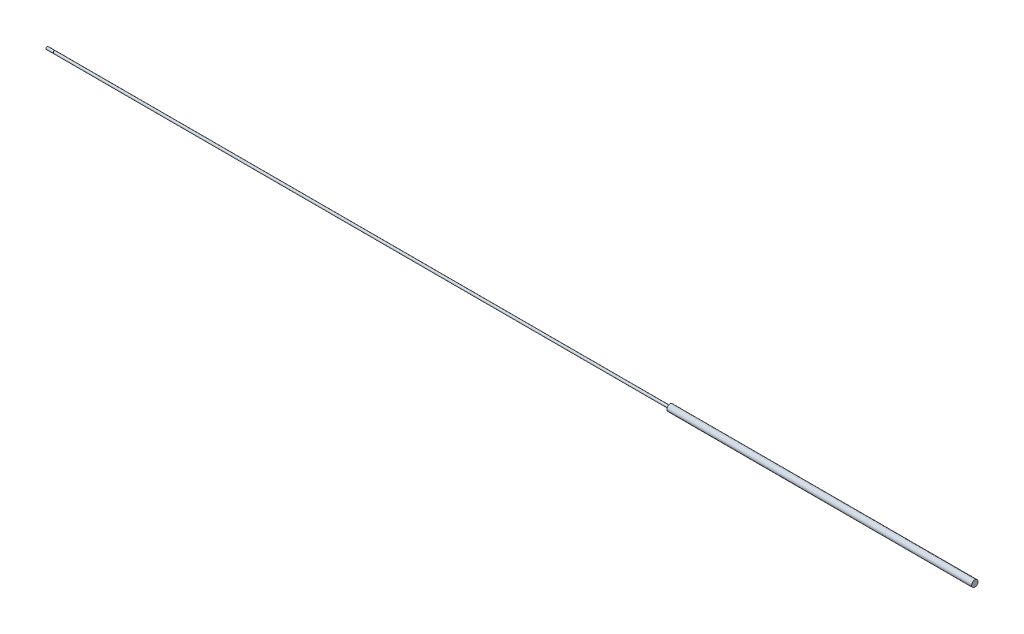
SolidWorks part; units mm, degrees
ref_plane "Front Plane" through (0, 0, 0) normal (0, 0, 1) x (1, 0, 0)
ref_plane "Top Plane" through (0, 0, 0) normal (0, 1, 0) x (1, 0, 0)
ref_plane "Right Plane" through (0, 0, 0) normal (1, 0, 0) x (0, 0, -1)
sketch "Sketch1" plane through (0, 0, 0) normal (0, 0, 1) x (1, 0, 0)
  line L0 (0, 0) -> (0, 1.5875)
  line L1 (0, 1.5875) -> (777.875, 1.5875)
  line L2 (777.875, 1.5875) -> (777.875, 4.0323)
  line L3 (777.875, 4.0323) -> (1163.1168, 4.0323)
  line L4 (1163.1168, 4.0323) -> (1163.1168, 0)
  line L5 (1163.1168, 0) -> (0, 0)
  line L6 (1163.1168, 0) -> (0, 0) construction
revolve "Revolve1" add sketch "Sketch1" angle 360 about L6 reverse direction yes
cosmetic thread "Cosmetic Thread1" parameters "D1"=9.652, "D2"=2.4181
sketch "Sketch2" plane through (0, 0, 0) normal (0, 0, 1) x (1, 0, 0)
  line L0 (-9.652, 0) -> (-9.652, 1.209)
  line L1 (-9.652, 1.209) -> (-9.2735, 1.5875)
  line L2 (-9.2735, 1.5875) -> (0, 1.5875)
  line L3 (0, 1.5875) -> (0, 0)
  line L4 (0, 0) -> (-9.652, 0)
  line L5 (0, 0) -> (-9.652, 0) construction
revolve "Revolve2" add sketch "Sketch2" angle 360 about L5 reverse direction yes
ref_plane "Plane1" through (0, 0, 0) normal (1, 0, 0) x (0, 0, -1)
ref_plane "Plane2" through (0, 0, 0) normal (1, 0, 0) x (0, 0, -1)
ref_plane "Plane3" through (1940.9918, 0, 0) normal (1, 0, 0) x (0, 0, -1)
ref_plane "Plane4" through (-9.652, 0, 0) normal (1, 0, 0) x (0, 0, -1)
sketch "Sketch3" plane through (0, 0, 0) normal (0, 0, 1) x (1, 0, 0)
  line L0 (-0.254, 1.8415) -> (-0.254, 1.3335)
  line L1 (-0.254, 1.3335) -> (0, 1.3335)
  line L2 (0, 1.3335) -> (0, 1.8415)
  line L3 (0, 1.8415) -> (-0.254, 1.8415)
  line L4 (0, 0) -> (-0.254, 0) construction
revolve "Cut-Revolve1" cut sketch "Sketch3" angle 360 about L4 reverse direction yes
ref_plane "Plane5" through (0, 0, 0) normal (1, 0, 0) x (0, 0, -1)
ref_plane "Plane6" through (-9.652, 0, 0) normal (1, 0, 0) x (0, 0, -1)
ref_plane "dia1 XY" through (0, 0, 0) normal (1, 0, 0) x (0, 0, -1)
ref_plane "dia1 XZ" through (0, 1.5875, 0) normal (0, -1, 0) x (-1, 0, 0)
ref_plane "dia1 YZ" through (0, 0, 0) normal (0, 0, -1) x (-1, 0, 0)
ref_axis "dia1 X" through (0, 1.5875, 80.9) along (0, 0, -1)
ref_axis "dia1 Y" through (0, -50, 0) along (0, 1, 0)
ref_axis "dia1 Z" through (80.9, 1.5875, 0) along (-1, 0, 0)
sketch3d "dia1"
  point P0 (0, 1.5875, 0)
ref_plane "dia12 XY" through (0, 0, 0) normal (1, 0, 0) x (0, 0, -1)
ref_plane "dia12 XZ" through (0, 0, 0) normal (0, -1, 0) x (-1, 0, 0)
ref_plane "dia12 YZ" through (0, 0, 4.5593) normal (0, 0, -1) x (-1, 0, 0)
ref_axis "dia12 X" through (0, 0, 80.9) along (0, 0, -1)
ref_axis "dia12 Y" through (0, -50, 4.5593) along (0, 1, 0)
ref_axis "dia12 Z" through (80.9, 0, 4.5593) along (-1, 0, 0)
sketch3d "dia12"
  point P0 (0, 0, 4.5593)
ref_plane "dia2 XY" through (0, 0, 0) normal (1, 0, 0) x (0, 0, -1)
ref_plane "dia2 XZ" through (0, -1.5875, 0) normal (0, -1, 0) x (-1, 0, 0)
ref_plane "dia2 YZ" through (0, 0, 0) normal (0, 0, -1) x (-1, 0, 0)
ref_axis "dia2 X" through (0, -1.5875, 80.9) along (0, 0, -1)
ref_axis "dia2 Y" through (0, -50, 0) along (0, 1, 0)
ref_axis "dia2 Z" through (80.9, -1.5875, 0) along (-1, 0, 0)
sketch3d "dia2"
  point P0 (0, -1.5875, 0)
ref_plane "dia22 XY" through (0, 0, 0) normal (1, 0, 0) x (0, 0, -1)
ref_plane "dia22 XZ" through (0, 0, 0) normal (0, -1, 0) x (-1, 0, 0)
ref_plane "dia22 YZ" through (0, 0, -4.5593) normal (0, 0, -1) x (-1, 0, 0)
ref_axis "dia22 X" through (0, 0, 80.9) along (0, 0, -1)
ref_axis "dia22 Y" through (0, -50, -4.5593) along (0, 1, 0)
ref_axis "dia22 Z" through (80.9, 0, -4.5593) along (-1, 0, 0)
sketch3d "dia22"
  point P0 (0, 0, -4.5593)
ref_plane "rl1 XY" through (-9.652, 0, 0) normal (1, 0, 0) x (0, 0, -1)
ref_plane "rl1 XZ" through (0, 0, 0) normal (0, -1, 0) x (-1, 0, 0)
ref_plane "rl1 YZ" through (0, 0, 0) normal (0, 0, -1) x (-1, 0, 0)
ref_axis "rl1 X" through (-9.652, 0, 80.9) along (0, 0, -1)
ref_axis "rl1 Y" through (-9.652, -50, 0) along (0, 1, 0)
ref_axis "rl1 Z" through (80.9, 0, 0) along (-1, 0, 0)
sketch3d "rl1"
  point P0 (-9.652, 0, 0)
ref_plane "rl2 XY" through (0, 0, 0) normal (1, 0, 0) x (0, 0, -1)
ref_plane "rl2 XZ" through (0, 0, 0) normal (0, -1, 0) x (-1, 0, 0)
ref_plane "rl2 YZ" through (0, 0, 0) normal (0, 0, -1) x (-1, 0, 0)
ref_axis "rl2 X" through (0, 0, 80.9) along (0, 0, -1)
ref_axis "rl2 Y" through (0, -50, 0) along (0, 1, 0)
ref_axis "rl2 Z" through (80.9, 0, 0) along (-1, 0, 0)
sketch3d "rl2"
  point P0 (0, 0, 0)
ref_plane "rod_cp XY" through (0, 0, 0) normal (1, 0, 0) x (0, 0, -1)
ref_plane "rod_cp XZ" through (0, 0, 0) normal (0, -1, 0) x (-1, 0, 0)
ref_plane "rod_cp YZ" through (0, 0, 0) normal (0, 0, -1) x (-1, 0, 0)
ref_axis "rod_cp X" through (0, 0, 80.9) along (0, 0, -1)
ref_axis "rod_cp Y" through (0, -50, 0) along (0, 1, 0)
ref_axis "rod_cp Z" through (80.9, 0, 0) along (-1, 0, 0)
sketch3d "rod_cp"
  point P0 (0, 0, 0)
ref_plane "thd1 XY" through (-9.652, 0, 0) normal (1, 0, 0) x (0, 0, -1)
ref_plane "thd1 XZ" through (0, 1.5875, 0) normal (0, -1, 0) x (-1, 0, 0)
ref_plane "thd1 YZ" through (0, 0, 0) normal (0, 0, -1) x (-1, 0, 0)
ref_axis "thd1 X" through (-9.652, 1.5875, 80.9) along (0, 0, -1)
ref_axis "thd1 Y" through (-9.652, -50, 0) along (0, 1, 0)
ref_axis "thd1 Z" through (80.9, 1.5875, 0) along (-1, 0, 0)
sketch3d "thd1"
  point P0 (-9.652, 1.5875, 0)
ref_plane "thd2 XY" through (-9.652, 0, 0) normal (1, 0, 0) x (0, 0, -1)
ref_plane "thd2 XZ" through (0, -1.5875, 0) normal (0, -1, 0) x (-1, 0, 0)
ref_plane "thd2 YZ" through (0, 0, 0) normal (0, 0, -1) x (-1, 0, 0)
ref_axis "thd2 X" through (-9.652, -1.5875, 80.9) along (0, 0, -1)
ref_axis "thd2 Y" through (-9.652, -50, 0) along (0, 1, 0)
ref_axis "thd2 Z" through (80.9, -1.5875, 0) along (-1, 0, 0)
sketch3d "thd2"
  point P0 (-9.652, -1.5875, 0)
ref_plane "to_rod_clevis XY" through (-9.652, 0, 0) normal (1, 0, 0) x (0, 0, -1)
ref_plane "to_rod_clevis XZ" through (0, 0, 0) normal (0, -1, 0) x (-1, 0, 0)
ref_plane "to_rod_clevis YZ" through (0, 0, 0) normal (0, 0, -1) x (-1, 0, 0)
ref_axis "to_rod_clevis X" through (-9.652, 0, 80.9) along (0, 0, -1)
ref_axis "to_rod_clevis Y" through (-9.652, -50, 0) along (0, 1, 0)
ref_axis "to_rod_clevis Z" through (80.9, 0, 0) along (-1, 0, 0)
sketch3d "to_rod_clevis"
  point P0 (-9.652, 0, 0)
